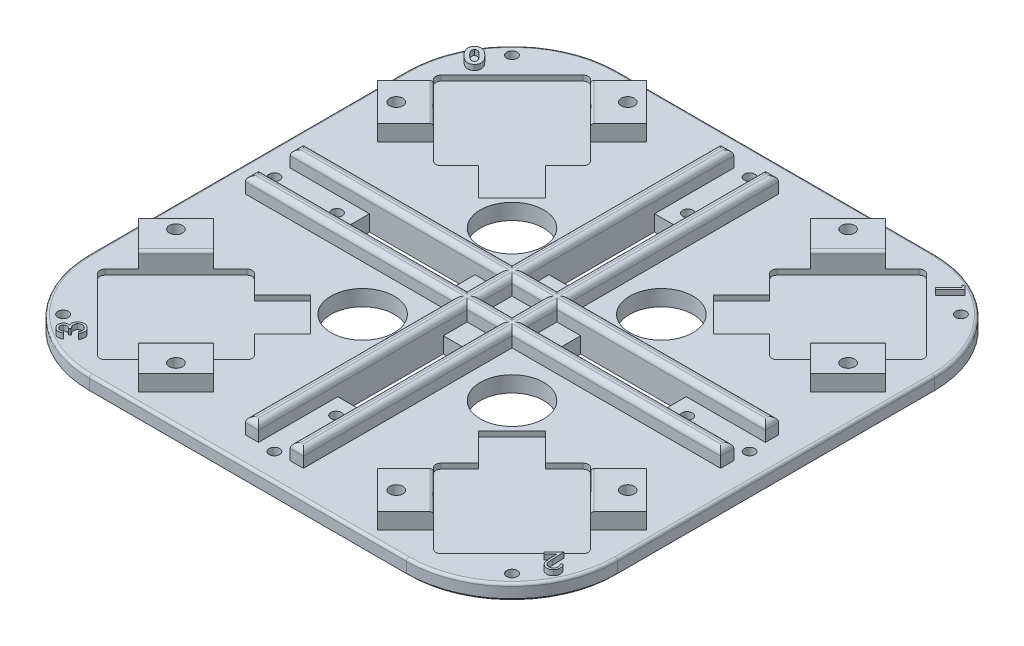
SolidWorks part; units mm, degrees
ref_plane "Спереди" through (0, 0, 0) normal (0, 0, 1) x (1, 0, 0)
ref_plane "Сверху" through (0, 0, 0) normal (0, 1, 0) x (1, 0, 0)
ref_plane "Справа" through (0, 0, 0) normal (1, 0, 0) x (0, 0, -1)
sketch "Эскиз1" plane through (0, 0, 0) normal (0, 1, 0) x (1, 0, 0)
  line L1 (-100, -100) -> (100, -100)
  line L2 (-100, -100) -> (-100, 100)
  line L3 (-100, 100) -> (100, 100)
  line L4 (100, -100) -> (100, 100)
  line L5 (0, 100) -> (0, -100) construction
  line L6 (-100, 0) -> (100, 0) construction
  line L11 (0, 75) -> (0, -75) construction
  line L12 (-39.5, 0) -> (39.5, 0) construction
  line L13 (-85, -85) -> (85, -85) construction
  line L14 (-85, -85) -> (-85, 85) construction
  line L15 (-85, 85) -> (85, 85) construction
  line L16 (85, -85) -> (85, 85) construction
  line L17 (0, 85) -> (0, -85) construction
  line L18 (-85, 0) -> (85, 0) construction
  circle A8 centre (-90, 0) radius 2
  circle A9 centre (0, 90) radius 2
  circle A10 centre (90, 0) radius 2
  circle A11 centre (0, -90) radius 2
  circle A12 centre (-85, 85) radius 2
  circle A13 centre (85, 85) radius 2
  circle A14 centre (85, -85) radius 2
  circle A15 centre (-85, -85) radius 2
  point P0 (0, 0)
  point P4 (0, 0)
  point P11 (0, 0)
  point P27 (0, 0)
  dimension "D6" = 90
  dimension "D1" = 200
  dimension "D8" = 170
  dimension "D7" = 4
extrude "Бобышка-Вытянуть1" add sketch "Эскиз1" along normal blind 6
sketch "Эскиз2" plane through (0, 6, 0) normal (0, 1, 0) x (1, 0, 0)
  line L0 (0, 72.2532) -> (0, 0) construction
  line L1 (0, 0) -> (100, 100) construction
  line L2 (63.6396, 33.9411) -> (33.9411, 63.6396)
  line L3 (63.6396, 33.9411) -> (93.3381, 63.6396)
  line L4 (33.9411, 63.6396) -> (63.6396, 93.3381)
  line L5 (93.3381, 63.6396) -> (63.6396, 93.3381)
  line L6 (63.6396, 33.9411) -> (63.6396, 93.3381) construction
  line L7 (33.9411, 63.6396) -> (93.3381, 63.6396) construction
  line L8 (33.9411, -63.6396) -> (63.6396, -33.9411)
  line L9 (33.9411, -63.6396) -> (63.6396, -93.3381)
  line L10 (63.6396, -93.3381) -> (93.3381, -63.6396)
  line L11 (63.6396, -33.9411) -> (93.3381, -63.6396)
  line L12 (-63.6396, -33.9411) -> (-33.9411, -63.6396)
  line L13 (-63.6396, -33.9411) -> (-93.3381, -63.6396)
  line L14 (-93.3381, -63.6396) -> (-63.6396, -93.3381)
  line L15 (-33.9411, -63.6396) -> (-63.6396, -93.3381)
  line L16 (-33.9411, 63.6396) -> (-63.6396, 33.9411)
  line L17 (-33.9411, 63.6396) -> (-63.6396, 93.3381)
  line L18 (-63.6396, 93.3381) -> (-93.3381, 63.6396)
  line L19 (-63.6396, 33.9411) -> (-93.3381, 63.6396)
  point P6 (63.6396, 63.6396)
  point P24 (0, 0)
  dimension "D1" = 42
  dimension "D2" = 90
  dimension "D3" = 4
extrude "Вырез-Вытянуть1" cut sketch "Эскиз2" against normal blind 2
fillet "Скругление1" radius 2 16 edges at (63.6396, 5, -33.9411) (33.9411, 5, -63.6396) (93.3381, 5, -63.6396) (63.6396, 5, -93.3381) (-63.6396, 5, -93.3381) (-63.6396, 5, -33.9411) (-93.3381, 5, -63.6396) (-33.9411, 5, -63.6396) (63.6396, 5, 93.3381) (93.3381, 5, 63.6396) (63.6396, 5, 33.9411) (33.9411, 5, 63.6396) (-63.6396, 5, 93.3381) (-33.9411, 5, 63.6396) (-63.6396, 5, 33.9411) (-93.3381, 5, 63.6396)
sketch "Эскиз3" plane through (0, 6, 0) normal (0, 1, 0) x (1, 0, 0)
  line L0 (48.7904, 48.7904) -> (67.3817, 67.3817) construction
  line L1 (35.3553, 62.2254) -> (62.2254, 35.3553) construction
  line L2 (48.7904, 78.4889) -> (78.4889, 48.7904) construction
  line L3 (62.2254, 91.9239) -> (35.3553, 65.0538) construction
  line L4 (65.0538, 35.3553) -> (91.9239, 62.2254) construction
  line L5 (41.7193, 71.4178) -> (55.8614, 85.5599)
  line L6 (41.7193, 71.4178) -> (31.1127, 82.0244)
  line L7 (55.8614, 85.5599) -> (45.2548, 96.1665)
  line L8 (31.1127, 82.0244) -> (45.2548, 96.1665)
  line L9 (62.2254, 91.9239) -> (35.3553, 65.0538) construction
  line L10 (85.5599, 55.8614) -> (96.1665, 45.2548)
  line L11 (82.0244, 31.1127) -> (96.1665, 45.2548)
  line L12 (71.4178, 41.7193) -> (82.0244, 31.1127)
  line L13 (71.4178, 41.7193) -> (85.5599, 55.8614)
  line L44 (65.0538, 35.3553) -> (91.9239, 62.2254) construction
  line L45 (0, 128.3294) -> (0, 0) construction
  line L64 (0, 0) -> (145.1139, 0) construction
  line L65 (62.2254, 91.9239) -> (35.3553, 65.0538) construction
  line L90 (48.7904, -78.4889) -> (78.4889, -48.7904) construction
  line L91 (48.7904, -48.7904) -> (67.3817, -67.3817) construction
  line L92 (71.4178, -41.7193) -> (85.5599, -55.8614)
  line L93 (71.4178, -41.7193) -> (82.0244, -31.1127)
  line L94 (82.0244, -31.1127) -> (96.1665, -45.2548)
  line L95 (85.5599, -55.8614) -> (96.1665, -45.2548)
  line L96 (31.1127, -82.0244) -> (45.2548, -96.1665)
  line L97 (55.8614, -85.5599) -> (45.2548, -96.1665)
  line L98 (41.7193, -71.4178) -> (31.1127, -82.0244)
  line L99 (41.7193, -71.4178) -> (55.8614, -85.5599)
  line L100 (-48.7904, -48.7904) -> (-67.3817, -67.3817) construction
  line L101 (-48.7904, -78.4889) -> (-78.4889, -48.7904) construction
  line L102 (-48.7904, 78.4889) -> (-78.4889, 48.7904) construction
  line L103 (-48.7904, 48.7904) -> (-67.3817, 67.3817) construction
  line L104 (-41.7193, -71.4178) -> (-55.8614, -85.5599)
  line L105 (-41.7193, -71.4178) -> (-31.1127, -82.0244)
  line L106 (-55.8614, -85.5599) -> (-45.2548, -96.1665)
  line L107 (-31.1127, -82.0244) -> (-45.2548, -96.1665)
  line L108 (-85.5599, -55.8614) -> (-96.1665, -45.2548)
  line L109 (-82.0244, -31.1127) -> (-96.1665, -45.2548)
  line L110 (-71.4178, -41.7193) -> (-82.0244, -31.1127)
  line L111 (-71.4178, -41.7193) -> (-85.5599, -55.8614)
  line L112 (-71.4178, 41.7193) -> (-85.5599, 55.8614)
  line L113 (-71.4178, 41.7193) -> (-82.0244, 31.1127)
  line L114 (-82.0244, 31.1127) -> (-96.1665, 45.2548)
  line L115 (-85.5599, 55.8614) -> (-96.1665, 45.2548)
  line L116 (-31.1127, 82.0244) -> (-45.2548, 96.1665)
  line L117 (-55.8614, 85.5599) -> (-45.2548, 96.1665)
  line L118 (-41.7193, 71.4178) -> (-31.1127, 82.0244)
  line L119 (-41.7193, 71.4178) -> (-55.8614, 85.5599)
  point P16 (48.7904, 78.4889)
  dimension "D1" = 20
  dimension "D2" = 15
extrude "Бобышка-Вытянуть3" add sketch "Эскиз3" along normal blind 6
fillet "Скругление4" radius 40 4 edges at (100, 3, -100) (100, 3, 100) (-100, 3, 100) (-100, 3, -100)
sketch "Эскиз4" plane through (0, 12, 0) normal (0, 1, 0) x (1, 0, 0)
  line L0 (89.0955, 38.1838) -> (38.1838, 89.0955) construction
  line L1 (82.0244, 31.1127) -> (96.1665, 45.2548) construction
  line L2 (45.2548, 96.1665) -> (31.1127, 82.0244) construction
  line L3 (41.7193, 71.4178) -> (55.8614, 85.5599) construction
  line L4 (48.7904, 48.7904) -> (78.4889, 78.4889) construction
  line L5 (35.3553, 62.2254) -> (62.2254, 35.3553) construction
  line L6 (91.9239, 65.0538) -> (65.0538, 91.9239) construction
  line L7 (0, 119.2498) -> (0, 0) construction
  line L8 (0, 0) -> (156.895, 0) construction
  line L9 (48.7904, -48.7904) -> (78.4889, -78.4889) construction
  line L10 (89.0955, -38.1838) -> (38.1838, -89.0955) construction
  line L11 (-89.0955, -38.1838) -> (-38.1838, -89.0955) construction
  line L12 (-48.7904, -48.7904) -> (-78.4889, -78.4889) construction
  line L13 (-48.7904, 48.7904) -> (-78.4889, 78.4889) construction
  line L14 (-89.0955, 38.1838) -> (-38.1838, 89.0955) construction
  circle A0 centre (41.7193, 85.5599) radius 2.5
  circle A1 centre (85.5599, 41.7193) radius 2.5
  circle A14 centre (85.5599, -41.7193) radius 2.5
  circle A15 centre (41.7193, -85.5599) radius 2.5
  circle A16 centre (-41.7193, -85.5599) radius 2.5
  circle A17 centre (-85.5599, -41.7193) radius 2.5
  circle A18 centre (-85.5599, 41.7193) radius 2.5
  circle A19 centre (-41.7193, 85.5599) radius 2.5
  dimension "D1" = 10
  dimension "D3" = 62
extrude "Вырез-Вытянуть2" cut sketch "Эскиз4" against normal blind 8
sketch "Эскиз5" plane through (0, 6, 0) normal (0, 1, 0) x (1, 0, 0)
  line L0 (0, 85.0414) -> (0, -87.3859) construction
  line L1 (-6, 90) -> (-11, 90)
  line L2 (111.3105, 0) -> (-132.9438, 0) construction
  line L3 (6, -90) -> (11, -90)
  line L4 (6, -90) -> (6, 90)
  line L5 (6, 90) -> (11, 90)
  line L6 (11, -90) -> (11, 90)
  line L7 (8.5, 90) -> (8.5, -90) construction
  line L8 (6, 0) -> (11, 0) construction
  line L9 (-11, -90) -> (-11, 90)
  line L10 (-6, -90) -> (-11, -90)
  line L11 (-6, -90) -> (-6, 90)
  line L12 (-6, 0) -> (-11, 0) construction
  line L13 (-8.5, 90) -> (-8.5, -90) construction
  point P3 (8.5, 0)
  point P13 (-8.5, 0)
  dimension "D1" = 5
  dimension "D2" = 180
  dimension "D3" = 12
extrude "Бобышка-Вытянуть4" add sketch "Эскиз5" along normal blind 6
sketch "Эскиз6" plane through (0, 6, 0) normal (0, 1, 0) x (1, 0, 0)
  line L0 (-101.5062, 0) -> (110.1382, 0) construction
  line L1 (-90, -8.5) -> (90, -8.5) construction
  line L2 (-90, 11) -> (90, 11)
  line L3 (-90, 11) -> (-90, 6)
  line L4 (-90, 6) -> (90, 6)
  line L5 (90, 11) -> (90, 6)
  line L6 (0, 6) -> (0, 11) construction
  line L7 (-90, 8.5) -> (90, 8.5) construction
  line L8 (0, -6) -> (0, -11) construction
  line L9 (90, -11) -> (90, -6)
  line L10 (-90, -6) -> (90, -6)
  line L11 (-90, -11) -> (-90, -6)
  line L12 (-90, -11) -> (90, -11)
  point P3 (0, 8.5)
  point P15 (0, -8.5)
  dimension "D1" = 180
  dimension "D2" = 5
  dimension "D3" = 12
extrude "Бобышка-Вытянуть5" add sketch "Эскиз6" along normal blind 6
fillet "Скругление5" radius 2 32 edges at (-8.5, 12, 90) (-11, 12, -50.5) (-11, 12, 50.5) (-8.5, 12, -90) (-6, 12, -50.5) (-6, 12, 50.5) (8.5, 12, 90) (6, 12, -50.5) (6, 12, 50.5) (8.5, 12, -90) (11, 12, -50.5) (11, 12, 50.5) (0, 12, -6) (-6, 12, 0) (0, 12, 6) (6, 12, 0) (-50.5, 12, 11) (-90, 12, 8.5) (-50.5, 12, 6) (-11, 12, 0) (-50.5, 12, -6) (-90, 12, -8.5) (-50.5, 12, -11) (0, 12, -11) (50.5, 12, -11) (90, 12, -8.5) (50.5, 12, -6) (11, 12, 0) (50.5, 12, 6) (90, 12, 8.5) (50.5, 12, 11) (0, 12, 11)
sketch "Эскиз7" plane through (0, 6, 0) normal (0, 1, 0) x (1, 0, 0)
  line L0 (0, 76.3028) -> (0, 0) construction
  line L1 (0, 0) -> (74.3797, 74.3797) construction
  line L2 (20, 6) -> (60, 6)
  line L3 (-6, 20) -> (6, 20)
  line L4 (-6, 20) -> (-6, 60)
  line L5 (-6, 60) -> (6, 60)
  line L6 (6, 20) -> (6, 60)
  line L7 (0, 60) -> (0, 20) construction
  line L8 (-6, 40) -> (6, 40) construction
  line L9 (20, 6) -> (20, -6)
  line L10 (20, -6) -> (60, -6)
  line L11 (60, 6) -> (60, -6)
  line L12 (6, -20) -> (6, -60)
  line L13 (6, -20) -> (-6, -20)
  line L14 (-6, -20) -> (-6, -60)
  line L15 (6, -60) -> (-6, -60)
  line L16 (-20, -6) -> (-60, -6)
  line L17 (-20, -6) -> (-20, 6)
  line L18 (-20, 6) -> (-60, 6)
  line L19 (-60, -6) -> (-60, 6)
  circle A0 centre (28.2843, 28.2843) radius 12
  circle A1 centre (28.2843, -28.2843) radius 12
  circle A2 centre (-28.2843, -28.2843) radius 12
  circle A3 centre (-28.2843, 28.2843) radius 12
  point P6 (0, 40)
  point P15 (0, 0)
  point P32 (0, 0)
  dimension "D1" = 40
  dimension "D2" = 24
  dimension "D4" = 12
  dimension "D5" = 40
  dimension "D6" = 40
  dimension "D3" = 4
  dimension "D7" = 4
extrude "Вырез-Вытянуть3" cut sketch "Эскиз7" against normal blind 6
sketch "Эскиз8" plane through (0, 6, 0) normal (0, 1, 0) x (1, 0, 0)
  line L0 (48.7904, 48.7904) -> (72.3205, 72.3205) construction
  line L1 (35.3553, 62.2254) -> (62.2254, 35.3553) construction
  line L2 (44.5477, 31.8198) -> (31.8198, 44.5477)
  line L3 (44.5477, 31.8198) -> (65.7609, 53.033)
  line L4 (31.8198, 44.5477) -> (53.033, 65.7609)
  line L5 (65.7609, 53.033) -> (53.033, 65.7609)
  line L6 (44.5477, 31.8198) -> (53.033, 65.7609) construction
  line L7 (31.8198, 44.5477) -> (65.7609, 53.033) construction
  line L20 (0, 107.5006) -> (0, 0) construction
  line L21 (0, 0) -> (140.6034, 0) construction
  line L22 (31.8198, -44.5477) -> (65.7609, -53.033) construction
  line L23 (44.5477, -31.8198) -> (53.033, -65.7609) construction
  line L24 (48.7904, -48.7904) -> (72.3205, -72.3205) construction
  line L25 (65.7609, -53.033) -> (53.033, -65.7609)
  line L26 (31.8198, -44.5477) -> (53.033, -65.7609)
  line L27 (44.5477, -31.8198) -> (65.7609, -53.033)
  line L28 (44.5477, -31.8198) -> (31.8198, -44.5477)
  line L29 (-48.7904, -48.7904) -> (-72.3205, -72.3205) construction
  line L30 (-44.5477, -31.8198) -> (-53.033, -65.7609) construction
  line L31 (-31.8198, -44.5477) -> (-65.7609, -53.033) construction
  line L32 (-31.8198, 44.5477) -> (-65.7609, 53.033) construction
  line L33 (-44.5477, 31.8198) -> (-53.033, 65.7609) construction
  line L34 (-48.7904, 48.7904) -> (-72.3205, 72.3205) construction
  line L35 (-44.5477, -31.8198) -> (-31.8198, -44.5477)
  line L36 (-44.5477, -31.8198) -> (-65.7609, -53.033)
  line L37 (-31.8198, -44.5477) -> (-53.033, -65.7609)
  line L38 (-65.7609, -53.033) -> (-53.033, -65.7609)
  line L39 (-65.7609, 53.033) -> (-53.033, 65.7609)
  line L40 (-31.8198, 44.5477) -> (-53.033, 65.7609)
  line L41 (-44.5477, 31.8198) -> (-65.7609, 53.033)
  line L42 (-44.5477, 31.8198) -> (-31.8198, 44.5477)
  point P24 (0, 16.9706)
  dimension "D1" = 18
  dimension "D2" = 30
extrude "Вырез-Вытянуть4" cut sketch "Эскиз8" against normal blind 2
fillet "Скругление6" radius 1 8 edges at (78.4889, 12, -48.7904) (48.7904, 12, -78.4889) (-78.4889, 12, 48.7904) (-48.7904, 12, 78.4889) (48.7904, 12, 78.4889) (78.4889, 12, 48.7904) (-78.4889, 12, -48.7904) (-48.7904, 12, -78.4889)
sketch "Эскиз9" plane through (0, 6, 0) normal (0, 1, 0) x (1, 0, 0)
  line L0 (-70.7105, 0.151) -> (0.151, 70.7105) construction
  line L1 (-70.7105, 0.151) -> (-0.151, -70.7105) construction
  line L2 (0.151, 70.7105) -> (70.7105, -0.151) construction
  line L3 (-0.151, -70.7105) -> (70.7105, -0.151) construction
  line L4 (-70.7105, 0.151) -> (70.7105, -0.151) construction
  line L5 (0.151, 70.7105) -> (-0.151, -70.7105) construction
  line L6 (0, 0) -> (60.8554, 60.8554) construction
  circle A0 centre (0.1419, 66.4679) radius 2
  circle A4 centre (-0.1419, -66.4679) radius 2
  circle A5 centre (66.4679, -0.1419) radius 2
  circle A6 centre (-66.4679, 0.1419) radius 2
  point P1 (0, 0)
  dimension "D2" = 4
  dimension "D3" = 3
  dimension "D4" = 3
  dimension "D5" = 94
  dimension "D1" = 100
extrude "Вырез-Вытянуть5" cut sketch "Эскиз9" against normal blind 10
sketch "Эскиз10" plane through (0, 6, 0) normal (0, 1, 0) x (1, 0, 0)
  line L0 (-89.4334, 70.8427) -> (-83.9454, 76.3307) construction
  line L1 (0, 108.5259) -> (0, 0) construction
  line L2 (71.3984, 88.9173) -> (76.8147, 83.501) construction
  line L3 (90.0364, -69.9365) -> (84.274, -75.6989) construction
  line L4 (-72.0522, -89.0668) -> (-79.6906, -81.6618) construction
  text T0 "<b>0</b>\r\n" font "Century Gothic" height 8
  text T1 "1\r\n" font "Century Gothic" height 8
  text T2 "2" font "Century Gothic" height 8
  text T3 "3\r\n" font "Century Gothic" height 8
extrude "Бобышка-Вытянуть6" add sketch "Эскиз10" along normal blind 2
fillet "Скругление9" radius 1 8 edges at (88.2843, 6, 88.2843) (0, 6, 100) (-88.2843, 6, 88.2843) (-100, 6, 0) (-88.2843, 6, -88.2843) (0, 6, -100) (88.2843, 6, -88.2843) (100, 6, 0)
chamfer "Фаска1" distance 1 angle 45 8 edges at (100, 0, 0) (88.2843, 0, -88.2843) (88.2843, 0, 88.2843) (0, 0, -100) (0, 0, 100) (-88.2843, 0, -88.2843) (-88.2843, 0, 88.2843) (-100, 0, 0)
